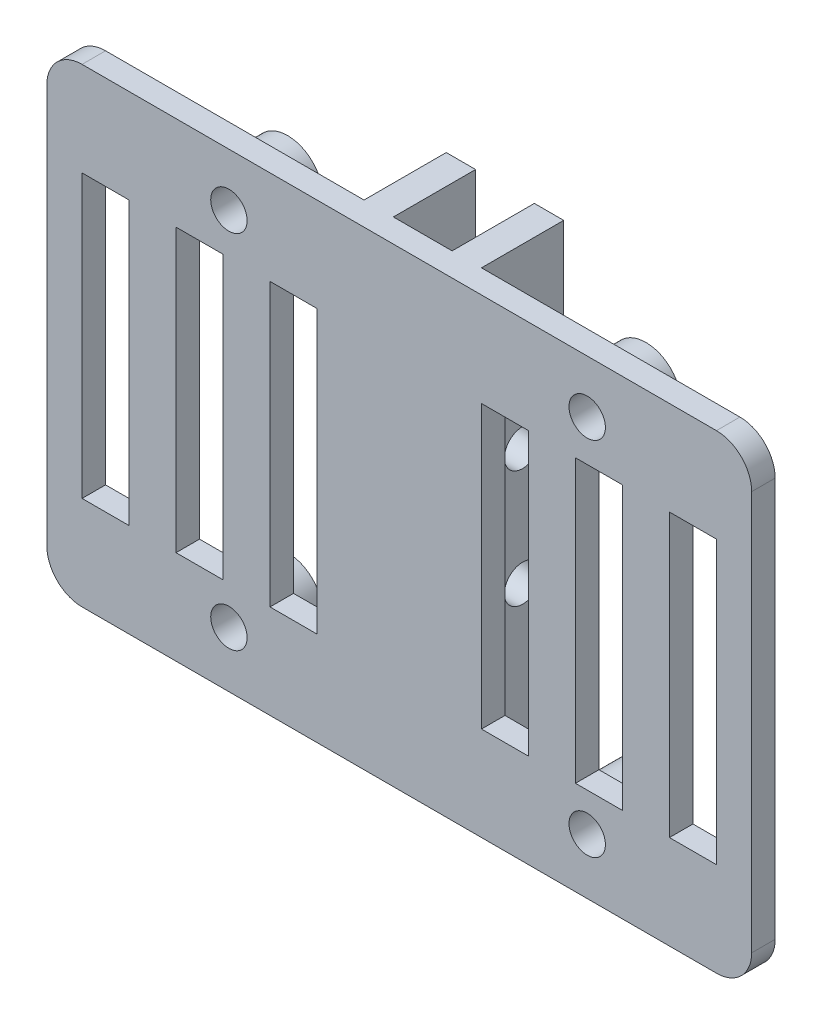
SolidWorks part; units mm, degrees
ref_plane "Plan de face" through (0, 0, 0) normal (0, 0, 1) x (1, 0, 0)
ref_plane "Plan de dessus" through (0, 0, 0) normal (0, 1, 0) x (1, 0, 0)
ref_plane "Plan de droite" through (0, 0, 0) normal (1, 0, 0) x (0, 0, -1)
sketch "Esquisse1" plane through (0, 0, 0) normal (0, 0, 1) x (1, 0, 0)
  line L1 (0, 0) -> (60, 0)
  line L2 (0, 0) -> (0, 40)
  line L3 (0, 40) -> (60, 40)
  line L4 (60, 0) -> (60, 40)
extrude "Boss.-Extru.1" add sketch "Esquisse1" along normal blind 9
sketch "Esquisse2" plane through (0, 0, 0) normal (0, 0, -1) x (-1, 0, 0)
  line L1 (-25, 40) -> (0, 40)
  line L2 (-25, 40) -> (-25, 0)
  line L3 (-25, 0) -> (0, 0)
  line L4 (0, 40) -> (0, 0)
  line L5 (-60, 40) -> (-35, 40)
  line L6 (-60, 40) -> (-60, 0)
  line L7 (-60, 0) -> (-35, 0)
  line L8 (-35, 40) -> (-35, 0)
  line L9 (-27.5, 40) -> (-32.5, 40)
  line L10 (-27.5, 40) -> (-27.5, 0)
  line L11 (-27.5, 0) -> (-32.5, 0)
  line L12 (-32.5, 40) -> (-32.5, 0)
extrude "Enlèv. mat.-Extru.1" cut sketch "Esquisse2" against normal blind 7
sketch "Esquisse3" plane through (35, 0, 0) normal (1, 0, 0) x (0, 0, -1)
  circle A0 centre (-3.5, 15) radius 1.55
  circle A1 centre (-3.5, 25) radius 1.55
extrude "Enlèv. mat.-Extru.2" cut sketch "Esquisse3" against normal through all
fillet "Congé1" radius 3 4 edges at (0, 0, 8) (60, 0, 8) (0, 40, 8) (60, 40, 8)
sketch "Esquisse9" plane through (0, 0, 7) normal (0, 0, -1) x (-1, 0, 0)
  circle A1 centre (-46, 35.5) radius 3
  circle A2 centre (-15.5, 35.5) radius 3
  circle A3 centre (-15.5, 4.75) radius 3
  circle A4 centre (-46, 4.75) radius 3
extrude "Boss.-Extru.2" add sketch "Esquisse9" along normal blind 3
sketch "Esquisse5" plane through (0, 0, 7) normal (0, 0, -1) x (-1, 0, 0)
  circle A0 centre (-46, 35.5) radius 1.55
  circle A1 centre (-46, 4.75) radius 1.55
  circle A2 centre (-15.5, 4.75) radius 1.55
  circle A3 centre (-15.5, 35.5) radius 1.55
extrude "Enlèv. mat.-Extru.4" cut sketch "Esquisse5" against normal through all both and the other way through all
sketch "Esquisse6" plane through (0, 0, 7) normal (0, 0, -1) x (-1, 0, 0)
  line L0 (-49, 32) -> (-45, 32)
  line L1 (-57, 32) -> (-53, 32)
  line L2 (-57, 32) -> (-57, 8)
  line L3 (-57, 8) -> (-53, 8)
  line L4 (-53, 32) -> (-53, 8)
  line L5 (-49, 32) -> (-49, 8)
  line L6 (-45, 32) -> (-45, 8)
  line L7 (-49, 8) -> (-45, 8)
  line L8 (-41, 32) -> (-37, 32)
  line L9 (-41, 32) -> (-41, 8)
  line L10 (-37, 32) -> (-37, 8)
  line L11 (-41, 8) -> (-37, 8)
  dimension "D1" = 3
sketch "Esquisse8" plane through (0, 0, 7) normal (0, 0, -1) x (-1, 0, 0)
  line L0 (-11, 32) -> (-11, 8)
  line L1 (-3, 32) -> (-7, 32)
  line L2 (-3, 32) -> (-3, 8)
  line L3 (-3, 8) -> (-7, 8)
  line L4 (-7, 32) -> (-7, 8)
  line L5 (-11, 32) -> (-15, 32)
  line L6 (-15, 32) -> (-15, 8)
  line L7 (-11, 8) -> (-15, 8)
  line L8 (-19, 32) -> (-19, 8)
  line L9 (-19, 32) -> (-23, 32)
  line L10 (-23, 32) -> (-23, 8)
  line L11 (-19, 8) -> (-23, 8)
  dimension "D1" = 3
extrude "Enlèv. mat.-Extru.5" cut sketch "Esquisse8" against normal blind 7
extrude "Enlèv. mat.-Extru.6" cut sketch "Esquisse6" against normal blind 7
